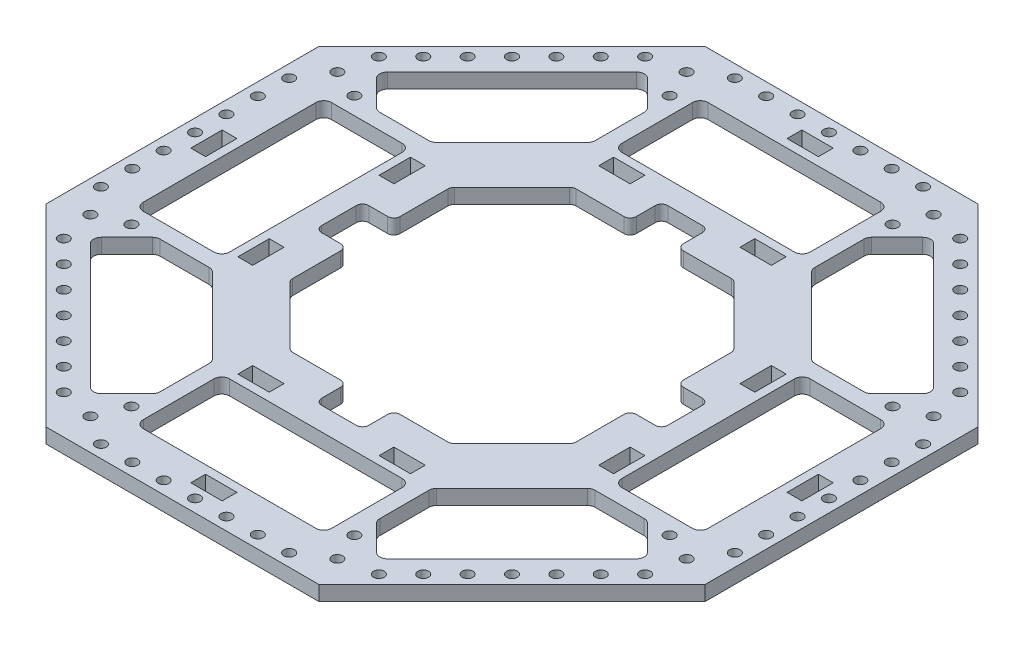
SolidWorks part; units mm, degrees
material "Custom Plastic"
ref_plane "Front Plane" through (0, 0, 0) normal (0, 0, 1) x (1, 0, 0)
ref_plane "Top Plane" through (0, 0, 0) normal (0, 1, 0) x (1, 0, 0)
ref_plane "Right Plane" through (0, 0, 0) normal (1, 0, 0) x (0, 0, -1)
ref_axis "Axis1" through (0, -18.6023, 0) along (0, 1, 0)
sketch "Base sketch" plane through (0, 0, 0) normal (0, 1, 0) x (1, 0, 0)
  line L1 (-127, 52.6051) -> (-127, -52.6051)
  line L2 (-127, -52.6051) -> (-52.6051, -127)
  line L3 (-52.6051, -127) -> (52.6051, -127)
  line L4 (52.6051, -127) -> (127, -52.6051)
  line L5 (127, -52.6051) -> (127, 52.6051)
  line L6 (127, 52.6051) -> (52.6051, 127)
  line L7 (52.6051, 127) -> (-52.6051, 127)
  line L8 (-52.6051, 127) -> (-127, 52.6051)
  circle A0 centre (0, 0) radius 127 construction
  dimension "D1" = 254
extrude "Base" add sketch "Base sketch" along normal blind 6
sketch "Sketch3" plane through (0, 6, 0) normal (0, 1, 0) x (1, 0, 0)
  line L0 (52.6051, 127) -> (-52.6051, 127) construction
  line L1 (-38.1, 114.3) -> (38.1, 114.3)
  line L2 (-38.1, 114.3) -> (-38.1, 79.375)
  line L4 (-38.1, 79.375) -> (38.1, 79.375)
  line L5 (38.1, 114.3) -> (38.1, 79.375)
  point P6 (0, 79.375)
  dimension "D1" = 76.2
  dimension "D2" = 34.925
  dimension "D3" = 12.7
extrude "Wheel cutout" cut sketch "Sketch3" against normal up to next
fillet "Wheel cutout fillets" radius 3.175 4 edges at (38.1, 3, -114.3) (38.1, 3, -79.375) (-38.1, 3, -79.375) (-38.1, 3, -114.3)
pattern_circular "Wheel cutout pattern" count 4 over 360 about axis through (0, -18.6023, 0) along (0, 1, 0) of "Wheel cutout", "Wheel cutout fillets"
sketch "Sketch4" plane through (0, 6, 0) normal (0, 1, 0) x (1, 0, 0)
  line L0 (0, 0) -> (0, 127) construction
  line L1 (52.6051, 127) -> (-52.6051, 127) construction
  line L2 (34.925, 120.65) -> (-34.925, 120.65) construction
  line L3 (-34.925, 123.65) -> (-22.225, 123.65) construction
  line L4 (-34.925, 123.65) -> (-34.925, 117.65) construction
  line L5 (-34.925, 117.65) -> (-22.225, 117.65) construction
  line L6 (-22.225, 123.65) -> (-22.225, 117.65) construction
  line L7 (-34.925, 123.65) -> (-22.225, 117.65) construction
  line L8 (-34.925, 117.65) -> (-22.225, 123.65) construction
  line L9 (34.925, 114.3) -> (-34.925, 114.3) construction
  line L10 (34.925, 117.65) -> (22.225, 123.65) construction
  line L11 (34.925, 123.65) -> (22.225, 117.65) construction
  line L12 (22.225, 123.65) -> (22.225, 117.65) construction
  line L13 (34.925, 117.65) -> (22.225, 117.65) construction
  line L14 (34.925, 123.65) -> (34.925, 117.65) construction
  line L15 (34.925, 123.65) -> (22.225, 123.65) construction
  line L16 (-38.1, 96.8375) -> (38.1, 96.8375) construction
  line L17 (-38.1, 111.125) -> (-38.1, 82.55) construction
  line L18 (38.1, 82.55) -> (38.1, 111.125) construction
  line L19 (34.925, 70.025) -> (22.225, 76.025) construction
  line L20 (34.925, 76.025) -> (22.225, 70.025) construction
  line L21 (-34.925, 76.025) -> (-22.225, 70.025) construction
  line L22 (-34.925, 70.025) -> (-22.225, 76.025) construction
  line L23 (34.925, 73.025) -> (-34.925, 73.025) construction
  line L24 (34.925, 70.025) -> (22.225, 70.025)
  line L25 (34.925, 70.025) -> (34.925, 76.025)
  line L26 (34.925, 76.025) -> (22.225, 76.025)
  line L27 (22.225, 70.025) -> (22.225, 76.025)
  line L28 (-22.225, 70.025) -> (-22.225, 76.025)
  line L29 (-34.925, 76.025) -> (-22.225, 76.025)
  line L30 (-34.925, 70.025) -> (-34.925, 76.025)
  line L31 (-34.925, 70.025) -> (-22.225, 70.025)
  line L33 (-6.35, 117.65) -> (6.35, 117.65)
  line L34 (-6.35, 117.65) -> (-6.35, 123.65)
  line L35 (-6.35, 123.65) -> (6.35, 123.65)
  line L36 (6.35, 117.65) -> (6.35, 123.65)
  line L37 (-6.35, 117.65) -> (6.35, 123.65) construction
  line L38 (-6.35, 123.65) -> (6.35, 117.65) construction
  point P5 (-28.575, 120.65)
  point P12 (0, 120.65)
  point P17 (28.575, 120.65)
  point P34 (28.575, 73.025)
  point P35 (-28.575, 73.025)
  point P38 (0, 120.65)
  dimension "D1" = 6
  dimension "D2" = 12.7
  dimension "D3" = 69.85
  dimension "D4" = 6.35
  dimension "D5" = 12.7
  dimension "D6" = 6
extrude "Support cutouts" cut sketch "Sketch4" against normal up to next
pattern_circular "Support cutout pattern" count 4 over 360 about axis through (0, -18.6023, 0) along (0, 1, 0) of "Support cutouts"
sketch "Sketch5" plane through (0, 6, 0) normal (0, 1, 0) x (1, 0, 0)
  line L0 (0, 0) -> (-89.8026, 89.8026) construction
  line L1 (-52.6051, 127) -> (-127, 52.6051) construction
  line L2 (-9.525, 70.025) -> (9.525, 70.025)
  line L3 (127, 52.6051) -> (52.6051, 127) construction
  line L4 (89.8026, 89.8026) -> (0, 0) construction
  line L6 (-9.525, 70.025) -> (-22.225, 70.025) construction
  line L10 (9.525, 70.025) -> (22.225, 70.025) construction
  line L12 (-22.225, 70.025) -> (-22.225, 76.025) construction
  line L13 (22.225, 76.025) -> (22.225, 70.025) construction
  line L15 (-9.525, 70.025) -> (-9.525, 57.325)
  line L16 (-9.525, 57.325) -> (-32.4776, 57.325)
  line L17 (-32.4776, 57.325) -> (-44.9013, 44.9013)
  line L19 (-44.9013, 44.9013) -> (0, 0)
  line L20 (0, 0) -> (44.9013, 44.9013)
  line L21 (44.9013, 44.9013) -> (32.4776, 57.325)
  line L22 (32.4776, 57.325) -> (9.525, 57.325)
  line L23 (9.525, 57.325) -> (9.525, 70.025)
  line L26 (-34.925, 70.025) -> (-22.225, 70.025) construction
  dimension "D4" = 63.5
  dimension "D2" = 19.05
  dimension "D3" = 12.7
extrude "Motor Clearance" cut sketch "Sketch5" against normal through all
pattern_circular "CirPattern1" count 4 every 90 about axis through (0, -18.6023, 0) along (0, 1, 0) of "Motor Clearance"
sketch "Sketch9" plane through (0, 6, 0) normal (0, 1, 0) x (1, 0, 0)
  line L0 (52.6051, 127) -> (-52.6051, 127) construction
  line L1 (-52.6051, 127) -> (-127, 52.6051) construction
  line L2 (-127, 52.6051) -> (-127, -52.6051) construction
  line L3 (-127, -52.6051) -> (-52.6051, -127) construction
  line L4 (-52.6051, -127) -> (52.6051, -127) construction
  line L5 (-127, -52.6051) -> (-120.65, -49.9749) construction
  line L6 (-55.2354, -133.35) -> (-52.6051, -127) construction
  line L7 (52.6051, -127) -> (127, -52.6051) construction
  line L8 (127, -52.6051) -> (127, 52.6051) construction
  line L9 (127, 52.6051) -> (52.6051, 127) construction
  line L10 (52.6051, 127) -> (-52.6051, 127)
  line L11 (-52.6051, 127) -> (-127, 52.6051)
  line L12 (-127, 52.6051) -> (-127, -52.6051)
  line L13 (-127, -52.6051) -> (-52.6051, -127)
  line L14 (-52.6051, -127) -> (52.6051, -127)
  line L15 (52.6051, -127) -> (127, -52.6051)
  line L16 (127, -52.6051) -> (127, 52.6051)
  line L17 (127, 52.6051) -> (52.6051, 127)
  line L18 (-55.2354, 133.35) -> (-133.35, 55.2354)
  line L19 (-133.35, 55.2354) -> (-133.35, -55.2354)
  line L20 (-133.35, -55.2354) -> (-55.2354, -133.35)
  line L21 (-55.2354, -133.35) -> (55.2354, -133.35)
  line L22 (55.2354, -133.35) -> (133.35, -55.2354)
  line L23 (133.35, -55.2354) -> (133.35, 55.2354)
  line L24 (133.35, 55.2354) -> (55.2354, 133.35)
  line L25 (55.2354, 133.35) -> (-55.2354, 133.35)
  line L26 (-52.6051, -127) -> (-49.9749, -120.65) construction
  line L27 (-133.35, -55.2354) -> (-127, -52.6051) construction
  line L28 (-127, 52.6051) -> (-120.65, 49.9749) construction
  line L29 (-133.35, 55.2354) -> (-127, 52.6051) construction
  line L30 (-52.6051, 127) -> (-49.9749, 120.65) construction
  line L31 (-55.2354, 133.35) -> (-52.6051, 127) construction
  line L32 (52.6051, 127) -> (49.9749, 120.65) construction
  line L33 (55.2354, 133.35) -> (52.6051, 127) construction
  line L34 (127, 52.6051) -> (120.65, 49.9749) construction
  line L35 (133.35, 55.2354) -> (127, 52.6051) construction
  line L36 (127, -52.6051) -> (120.65, -49.9749) construction
  line L37 (133.35, -55.2354) -> (127, -52.6051) construction
  line L38 (52.6051, -127) -> (49.9749, -120.65) construction
  line L39 (55.2354, -133.35) -> (52.6051, -127) construction
  line L40 (-120.65, -49.9749) -> (-108.9167, -45.1148) construction
  line L41 (-120.65, 49.9749) -> (-108.9167, 45.1148) construction
  line L42 (-49.9749, 120.65) -> (-45.1148, 108.9167) construction
  line L43 (49.9749, 120.65) -> (45.1148, 108.9167) construction
  line L44 (120.65, 49.9749) -> (108.9167, 45.1148) construction
  line L45 (120.65, -49.9749) -> (108.9167, -45.1148) construction
  line L46 (49.9749, -120.65) -> (45.1148, -108.9167) construction
  line L47 (-49.9749, -120.65) -> (-45.1148, -108.9167) construction
  point P41 (0, 0)
  point P55 (0, 0)
  dimension "D1" = 6.35
  dimension "D3" = 12.7
  dimension "D2" = 8
  dimension "D4" = 8
extrude "Extend for line sensor mount" add sketch "Sketch9" against normal through all contours L24 L25 L18 L19 L20 L21 L22 L23 L17 L16 L15 L14 L13 L12 L11 L10
hole_wizard "#8 Clearance Hole1" positions "Sketch20" profile "Sketch19" hole size "#8" standard "ANSI Inch" end condition through all
sketch "Sketch20" plane through (0, 6, 0) normal (0, 1, 0) x (1, 0, 0)
  point P31 (-49.9749, -120.65)
  point P34 (49.9749, -120.65)
  point P37 (120.65, -49.9749)
  point P40 (120.65, 49.9749)
  point P43 (-120.65, -49.9749)
  point P49 (-49.9749, 120.65)
  point P52 (49.9749, 120.65)
  point P58 (-120.65, 49.9749)
  point P61 (-108.9167, 45.1148)
  point P64 (-45.1148, 108.9167)
  point P67 (45.1148, 108.9167)
  point P70 (108.9167, 45.1148)
  point P73 (108.9167, -45.1148)
  point P76 (45.1148, -108.9167)
  point P79 (-45.1148, -108.9167)
  point P82 (-108.9167, -45.1148)
sketch "Sketch19" plane through (-49.9749, 6, 120.65) normal (1, 0, 0) x (0, 0, 1)
  line L0 (0, 0) -> (0, 6)
  line L1 (0, 6) -> (2.1526, 6)
  line L2 (2.1526, 6) -> (2.1526, 0)
  line L5 (2.1526, 0) -> (0, 0)
  line L11 (0, -6.35) -> (0, 107.95) construction
  dimension "Thru Hole Dia." = 4.3053
  dimension "Thru Hole Depth" = 6
sketch "light sensor mount" plane through (0, 6, 0) normal (0, 1, 0) x (1, 0, 0)
  line L0 (-55.2354, -133.35) -> (55.2354, -133.35) construction
  line L1 (-12.7, -128.27) -> (0, -128.27) construction
  line L2 (0, -128.27) -> (12.7, -128.27) construction
  line L3 (0, 0) -> (0, -128.27) construction
  line L6 (-12.7, -128.27) -> (-25.4, -128.27) construction
  line L7 (-25.4, -128.27) -> (-38.1, -128.27) construction
  line L8 (12.7, -128.27) -> (25.4, -128.27) construction
  line L9 (25.4, -128.27) -> (38.1, -128.27) construction
  line L10 (-38.1, -128.27) -> (-50.8, -128.27) construction
  line L11 (38.1, -128.27) -> (50.8, -128.27) construction
  dimension "D2" = 5.08
  dimension "D1" = 12.7
hole_wizard "light sensor mount holes" positions "Sketch16" profile "Sketch15" hole size "#8" standard "ANSI Inch" end condition through all
sketch "Sketch16" plane through (0, 6, 0) normal (0, 1, 0) x (1, 0, 0)
  point P0 (-12.7, -128.27)
  point P3 (0, -128.27)
  point P6 (12.7, -128.27)
  point P26 (25.4, -128.27)
  point P29 (38.1, -128.27)
  point P32 (-25.4, -128.27)
  point P35 (-38.1, -128.27)
sketch "Sketch15" plane through (-12.7, 6, 128.27) normal (1, 0, 0) x (0, 0, 1)
  line L0 (0, 0) -> (0, 6)
  line L1 (0, 6) -> (2.1526, 6)
  line L2 (2.1526, 6) -> (2.1526, 0)
  line L5 (2.1526, 0) -> (0, 0)
  line L11 (0, -6.35) -> (0, 107.95) construction
  dimension "Thru Hole Dia." = 4.3053
  dimension "Thru Hole Depth" = 6
pattern_circular "CirPattern7" count 8 over 360 about axis through (0, -18.6023, 0) along (0, 1, 0) of "light sensor mount holes"
fillet "Fillet1" radius 2.54 24 edges at (57.325, 3, -32.4776) (32.4776, 3, 57.325) (-32.4776, 3, 57.325) (-57.325, 3, 32.4776) (-70.025, 3, 9.525) (-9.525, 3, 70.025) (9.525, 3, 70.025) (70.025, 3, 9.525) (70.025, 3, -9.525) (57.325, 3, 9.525) (57.325, 3, 32.4776) (9.525, 3, 57.325) (-9.525, 3, 57.325) (-57.325, 3, 9.525) (57.325, 3, -9.525) (32.4776, 3, -57.325) (9.525, 3, -57.325) (-70.025, 3, -9.525) (-57.325, 3, -9.525) (-57.325, 3, -32.4776) (-9.525, 3, -70.025) (-9.525, 3, -57.325) (-32.4776, 3, -57.325) (9.525, 3, -70.025)
sketch "Sketch21" plane through (0, 6, 0) normal (0, 1, 0) x (1, 0, 0)
  line L1 (-112.7233, 57.9016) -> (-57.9016, 112.7233)
  line L2 (-57.9016, 112.7233) -> (-44.45, 99.2717)
  line L3 (-44.45, 99.2717) -> (-44.45, 76.7835)
  line L4 (-44.45, 76.7835) -> (-76.7835, 44.45)
  line L5 (-76.7835, 44.45) -> (-99.2717, 44.45)
  line L6 (-99.2717, 44.45) -> (-112.7233, 57.9016)
  line L7 (0, 0) -> (-60.6167, 60.6167) construction
  line L8 (-55.2354, 133.35) -> (-133.35, 55.2354) construction
  line L9 (-82.55, 38.1) -> (-111.125, 38.1) construction
  line L10 (-34.925, 79.375) -> (34.925, 79.375) construction
  line L11 (-32.8782, 79.375) -> (-79.375, 32.8782) construction
  line L12 (-79.375, 32.8782) -> (-79.375, -32.8782) construction
  line L13 (-79.375, -32.8782) -> (-32.8782, -79.375) construction
  line L14 (-32.8782, -79.375) -> (32.8782, -79.375) construction
  line L15 (32.8782, -79.375) -> (79.375, -32.8782) construction
  line L16 (79.375, -32.8782) -> (79.375, 32.8782) construction
  line L17 (79.375, 32.8782) -> (32.8782, 79.375) construction
  line L18 (32.8782, 79.375) -> (-32.8782, 79.375) construction
  circle A2 centre (-108.9167, 45.1148) radius 2.1527 construction
  circle A3 centre (0, 0) radius 79.375 construction
  dimension "D2" = 6.35
  dimension "D4" = 12.7
  dimension "D3" = 6.35
  dimension "D1" = 12.7
extrude "Cut-Extrude1" cut sketch "Sketch21" against normal through all
fillet "Fillet2" radius 3.175 6 edges at (-112.7233, 3, -57.9016) (-99.2717, 3, -44.45) (-76.7835, 3, -44.45) (-44.45, 3, -76.7835) (-44.45, 3, -99.2717) (-57.9016, 3, -112.7233)
pattern_circular "CirPattern8" count 4 every 90 about axis through (0, -18.6023, 0) along (0, 1, 0) of "Fillet2", "Cut-Extrude1"
equation "\"MAT_THICKNESS\"=0.23622"
equation "\"D1@Sketch4\"=\"MAT_THICKNESS\""
equation "\"D1@Base\"=\"MAT_THICKNESS\""
equation "\"D6@Sketch4\"=\"MAT_THICKNESS\""
equation "\"D3@Sketch4\"=2.75"
